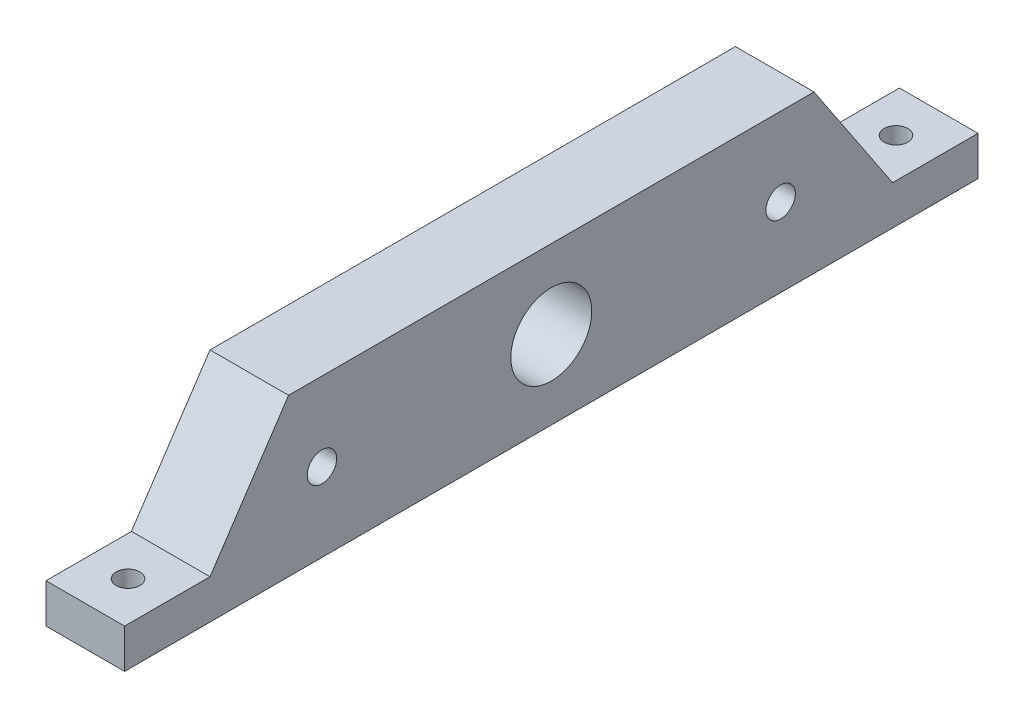
SolidWorks part; units mm, degrees
ref_plane "Front Plane" through (0, 0, 0) normal (0, 0, 1) x (1, 0, 0)
ref_plane "Top Plane" through (0, 0, 0) normal (0, 1, 0) x (1, 0, 0)
ref_plane "Right Plane" through (0, 0, 0) normal (1, 0, 0) x (0, 0, -1)
sketch "Sketch2" plane through (0, 0, 0) normal (1, 0, 0) x (0, 0, -1)
  line L1 (0, 0) -> (380, 0)
  line L2 (0, 0) -> (0, 40)
  line L3 (0, 40) -> (380, 40)
  line L4 (380, 0) -> (380, 40)
  line L5 (190, 0) -> (275.0005, 0)
  circle A2 centre (190, 20) radius 10.3017
  circle A3 centre (131.63, 20) radius 3.75
  circle A4 centre (248.37, 20) radius 3.75
extrude "Boss-Extrude2" add sketch "Sketch2" along normal blind 20 contours L1 L4 L3 L2 A2 region at (0, 20, -3.821)
sketch "Sketch3" plane through (0, 0, 0) normal (-1, 0, 0) x (0, 0, 1)
  line L0 (-190, 20) -> (-131.635, 20)
  line L1 (-190, 20) -> (-248.365, 20)
  dimension "D1" = 58.365
  dimension "D2" = 58.365
sketch "Sketch4" plane through (20, 0, 0) normal (1, 0, 0) x (0, 0, -1)
  line L1 (0, 0) -> (380, 0) construction
  line L3 (0, 40) -> (380, 40) construction
  line L4 (123.1292, 40) -> (0, 40)
  line L5 (0, 40) -> (0, 0)
  line L7 (103.136, 10) -> (123.1292, 40)
  line L12 (103.136, 10) -> (81.389, 10)
  line L13 (81.389, 10) -> (81.389, 0)
  line L14 (81.389, 0) -> (0, 0)
  line L16 (298.611, 10) -> (298.611, 0)
  line L17 (276.864, 10) -> (298.611, 10)
  line L18 (276.864, 10) -> (256.8708, 40)
  line L19 (256.8708, 40) -> (380, 40)
  line L20 (380, 40) -> (380, 0)
  line L21 (298.611, 0) -> (380, 0)
  line M9 (0, 0) -> (380, 0)
  line M10 (380, 0) -> (380, 40)
  line M11 (380, 40) -> (0, 40)
  line M12 (0, 40) -> (0, 0)
extrude "Cut-Extrude1" cut sketch "Sketch4" against normal blind 100 contours M9 M11 M12 | M9 M10 M11 region at (20, 21.4879, -53.6151) region at (20, 21.4879, -326.3849)
sketch "Sketch5" plane through (0, 10, 0) normal (0, 1, 0) x (1, 0, 0)
  circle A0 centre (10, 92.2625) radius 3.0234
  circle A1 centre (10, 287.7375) radius 3.0234
extrude "Cut-Extrude2" cut sketch "Sketch5" against normal through all both and the other way through all
